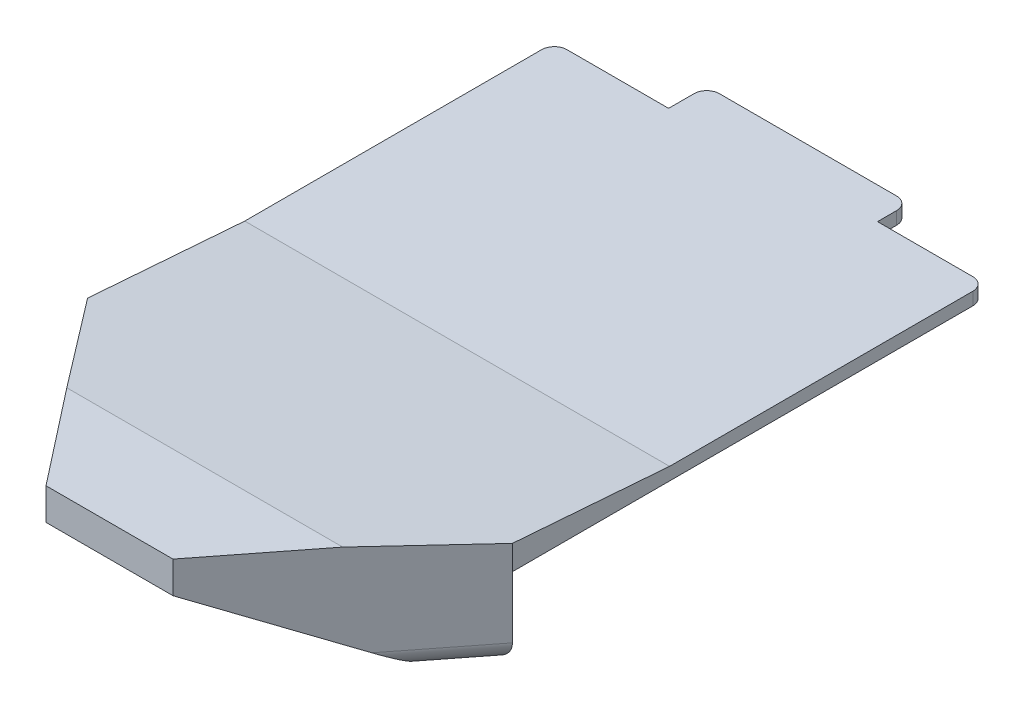
SolidWorks part; units mm, degrees
ref_plane "Front Plane" through (0, 0, 0) normal (0, 0, 1) x (1, 0, 0)
ref_plane "Top Plane" through (0, 0, 0) normal (0, 1, 0) x (1, 0, 0)
ref_plane "Right Plane" through (0, 0, 0) normal (1, 0, 0) x (0, 0, -1)
sketch "Sketch1" plane through (0, 0, 0) normal (0, 1, 0) x (1, 0, 0)
  line L0 (0, 0) -> (-16.35, 0)
  line L1 (-16.35, 0) -> (-16.35, -9.85)
  line L2 (-16.35, -9.85) -> (-2.6, -9.85)
  line L3 (-20.1, -33) -> (-20.1, -75)
  line L4 (-20.1, -75) -> (0, -75)
  line L5 (0, -75) -> (0, 0)
  line L6 (-2.6, -9.85) -> (-2.6, -33)
  line L7 (-2.6, -33) -> (-20.1, -33)
  dimension "D1" = 16.35
  dimension "D2" = 9.85
  dimension "D3" = 13.75
  dimension "D4" = 3.75
  dimension "D5" = 23.15
  dimension "D6" = 42
extrude "Boss-Extrude1" add sketch "Sketch1" along normal blind 7.7
sketch "Sketch2" plane through (0, 0, 75) normal (0, 0, 1) x (1, 0, 0)
  line L0 (-20.1, 7.7) -> (-20.1, 0) construction
  line L1 (-20.1, 5.1) -> (-13.1, 5.1)
  line L2 (-20.1, 5.1) -> (-20.1, 2)
  line L3 (-20.1, 2) -> (-13.1, 2)
  line L4 (-13.1, 5.1) -> (-13.1, 2)
  line L5 (-20.1, 0) -> (0, 0) construction
  dimension "D1" = 7
  dimension "D2" = 3.1
  dimension "D3" = 2
extrude "Cut-Extrude1" cut sketch "Sketch2" against normal through all
fillet "Fillet1" radius 10 1 edges at (-2.6, 3.85, 33)
sketch "Sketch3" plane through (0, 7.7, 0) normal (0, 1, 0) x (1, 0, 0)
  line L0 (0, 0) -> (0, -75)
  line L1 (0, -75) -> (-33.45, -75)
  line L2 (-33.45, -75) -> (-33.45, 0)
  line L3 (-33.45, 0) -> (0, 0)
  line L4 (0, -75) -> (0, -105)
  line L5 (0, -105) -> (-10, -105)
  line L6 (0, 0) -> (0, 4.5)
  line L7 (-33.45, -75) -> (-10, -105)
  line L8 (0, 4.5) -> (-33.45, 4.5)
  line L9 (-33.45, 4.5) -> (-33.45, 0)
  dimension "D1" = 33.45
  dimension "D2" = 30
  dimension "D3" = 10
  dimension "D4" = 4.5
extrude "Boss-Extrude2" add sketch "Sketch3" along normal blind 2
sketch "Sketch4" plane through (0, 0, 0) normal (1, 0, 0) x (0, 0, -1)
  line L0 (-105, 9.7) -> (-105, 12.7)
  line L1 (-105, 12.7) -> (-90, 12.7)
  line L2 (-90, 12.7) -> (-50.25, 9.7)
  line L3 (-105, 9.7) -> (4.5, 9.7) construction
  line L4 (-105, 9.7) -> (-50.25, 9.7)
  point P8 (-50.25, 9.7)
  dimension "D1" = 15
  dimension "D2" = 3
extrude "Boss-Extrude3" add sketch "Sketch4" against normal up to surface (33.45 mm away) up to face at (-33.45, 8.7, 35.25)
sketch "Sketch5" plane through (-33.45, 0, 0) normal (-1, 0, 0) x (0, 0, 1)
  line L0 (75, 7.7) -> (75, -5)
  line L1 (75, -5) -> (82, -5)
  line L2 (82, -5) -> (105, 7.7)
  line L3 (105, 7.7) -> (75, 7.7)
  line L4 (33, 0) -> (75, 0) construction
  dimension "D1" = 5
  dimension "D2" = 7
extrude "Boss-Extrude4" add sketch "Sketch5" against normal up to surface (33.45 mm away) up to face at (0, 7.56, 49.125)
sketch "Sketch6" plane through (0, 7.7, 0) normal (0, 1, 0) x (1, 0, 0)
  line L0 (-33.45, -75) -> (-10, -105)
  line L1 (-10, -105) -> (-33.45, -105)
  line L2 (-33.45, -105) -> (-33.45, -75)
extrude "Cut-Extrude2" cut sketch "Sketch6" against normal through all both and the other way through all
sketch "Sketch7" plane through (0, 0, 0) normal (1, 0, 0) x (0, 0, -1)
  line L0 (-75, 0) -> (-85, 0)
  line L1 (-85, 0) -> (-80, -5)
  line L2 (-82, -5) -> (-75, -5) construction
  line L3 (-80, -5) -> (-75, -5)
  line L4 (-75, -5) -> (-75, 0)
  dimension "D1" = 5
  dimension "D2" = 10
extrude "Cut-Extrude3" cut sketch "Sketch7" against normal blind 10
fillet "Fillet3" radius 1 2 edges at (-5, -5, 80) (-10, -5, 77.5)
fillet "Fillet4" [suppressed] radius 5
mirror "Mirror1" about plane through (0, 7.7, 75) normal (-1, 0, 0) of bodies 110
fillet "Fillet5" radius 3 2 edges at (-30.7142, -5, 78.5) (30.7142, -5, 78.5)
sketch "Sketch8" plane through (0, 9.7, 0) normal (0, 1, 0) x (1, 0, 0)
  line L0 (33.45, 4.5) -> (33.45, -0.5)
  line L1 (33.45, -50.25) -> (33.45, 4.5) construction
  line L2 (33.45, -0.5) -> (16.45, -0.5)
  line L3 (16.45, -0.5) -> (16.45, 4.5)
  line L4 (33.45, 4.5) -> (-33.45, 4.5) construction
  line L5 (16.45, 4.5) -> (33.45, 4.5)
  line L6 (0, 37.0905) -> (0, -37.0905) construction
  line L7 (-16.45, -0.5) -> (-16.45, 4.5) construction
  line L8 (-33.45, -0.5) -> (-16.45, -0.5) construction
  line L9 (-33.45, 4.5) -> (-33.45, -0.5) construction
  line L10 (-16.45, 4.5) -> (-33.45, 4.5) construction
  line L11 (-15.45, -1.5) -> (-15.45, 5.5)
  line L12 (-15.45, 5.5) -> (-34.45, 5.5)
  line L13 (-34.45, 5.5) -> (-34.45, -1.5)
  line L14 (-34.45, -1.5) -> (-15.45, -1.5)
  point P13 (0, 0)
  dimension "D1" = 5
  dimension "D2" = 17
  dimension "D3" = 1
extrude "Cut-Extrude4" cut sketch "Sketch8" against normal up to surface (9.7 mm away) up to face at (0, 0, 38.419)
fillet "Fillet6" radius 2 2 edges at (-15.45, 8.7, -4.5) (-33.45, 8.7, 1.5)
fillet "Fillet7" radius 2 2 edges at (33.45, 8.7, 0.5) (16.45, 8.7, -4.5)
